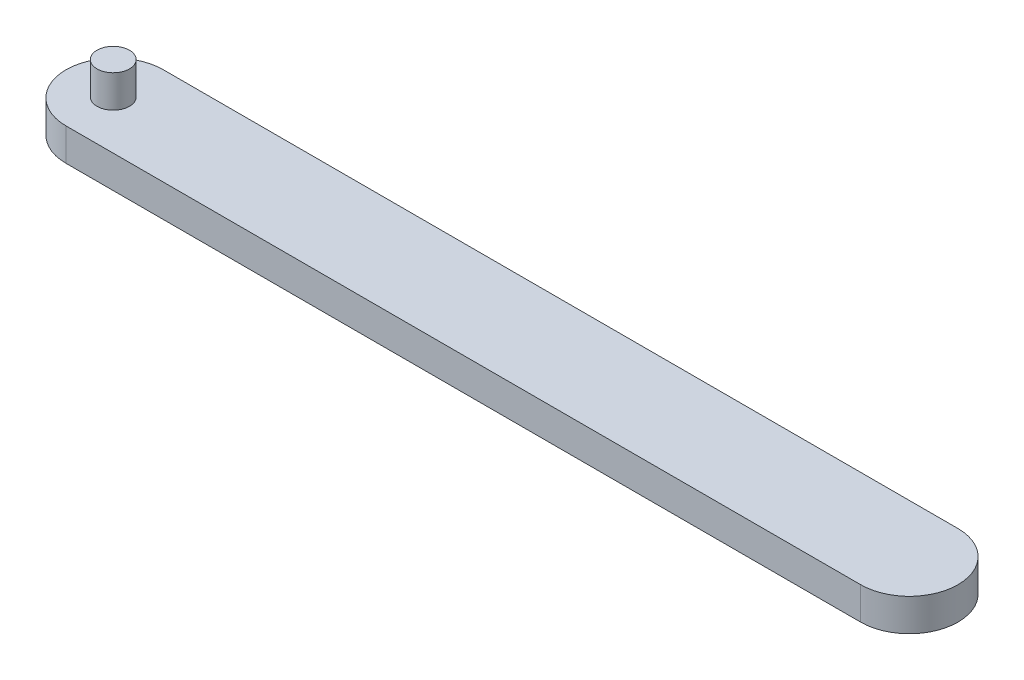
SolidWorks part; units mm, degrees
ref_plane "Front Plane" through (0, 0, 0) normal (0, 0, 1) x (1, 0, 0)
ref_plane "Top Plane" through (0, 0, 0) normal (0, 1, 0) x (1, 0, 0)
ref_plane "Right Plane" through (0, 0, 0) normal (1, 0, 0) x (0, 0, -1)
sketch "Sketch2" plane through (0, 0, 0) normal (0, 1, 0) x (1, 0, 0)
  line L1 (34.925, -3.81) -> (-34.925, -3.81)
  line L2 (34.925, -3.81) -> (34.925, 3.81)
  line L3 (34.925, 3.81) -> (-34.925, 3.81)
  line L4 (-34.925, -3.81) -> (-34.925, 3.81)
  line L5 (34.925, -3.81) -> (-34.925, 3.81) construction
  line L6 (34.925, 3.81) -> (-34.925, -3.81) construction
  point P0 (0, 0)
  dimension "D1" = 69.85
  dimension "D2" = 7.62
extrude "Boss-Extrude1" add sketch "Sketch2" along normal blind 2.54
fillet "Fillet1" 2 edges at (34.925, 1.27, 3.81) (34.925, 1.27, -3.81) type full round first side face at (0, 1.27, 3.81) second side face at (0, 1.27, -3.81) middle face at (34.925, 1.27, 0)
fillet "Fillet2" 2 edges at (-34.925, 1.27, -3.81) (-34.925, 1.27, 3.81) type full round first side face at (-1.905, 1.27, -3.81) second side face at (-1.905, 1.27, 3.81) middle face at (-34.925, 1.27, 0)
sketch "Sketch3" plane through (0, 2.54, 0) normal (0, 1, 0) x (1, 0, 0)
  circle A0 centre (-31.2277, 0) radius 1.27
extrude "Boss-Extrude2" add sketch "Sketch3" along normal blind 2.54
